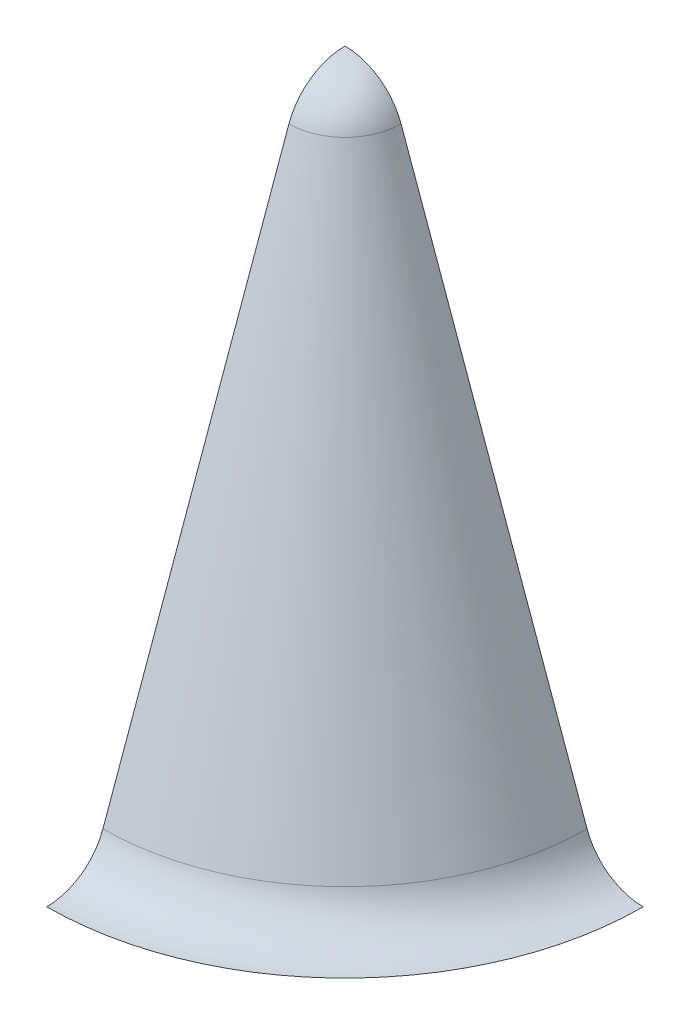
SolidWorks part; units mm, degrees
ref_plane "Ebene vorne" through (0, 0, 0) normal (0, 0, 1) x (1, 0, 0)
ref_plane "Ebene oben" through (0, 0, 0) normal (0, 1, 0) x (1, 0, 0)
ref_plane "Ebene rechts" through (0, 0, 0) normal (1, 0, 0) x (0, 0, -1)
sketch "Skizze2" plane through (0, 0, 0) normal (1, 0, 0) x (0, 0, -1)
  line L0 (0, 0) -> (1000, 0)
  line L1 (1000, 0) -> (1000, 2000)
  line L2 (1000, 2000) -> (1823.9706, 2000) construction
  line L3 (0, 0) -> (-711.6365, 0) construction
  line L4 (188.2165, 132.3647) -> (811.7835, 1867.6353)
  arc A0 (1000, 2000) -> (811.7835, 1867.6353) centre (1000, 1800) ccw
  arc A1 (0, 0) -> (188.2165, 132.3647) centre (0, 200) ccw
  point P10 (468.2367, 420.6035)
  dimension "D3" = 200
  dimension "D4" = 200
  dimension "D1" = 2000
  dimension "D2" = 1000
revolve "Rotation1" add sketch "Skizze2" angle 360 about L1
sketch "Skizze3" plane through (0, 0, 0) normal (0, 1, 0) x (1, 0, 0)
  line L0 (0, 0) -> (0, 1000)
  line L1 (0, 1000) -> (1000, 1000)
  arc A0 (0, 0) -> (1000, 1000) centre (0, 1000) cw
  dimension "D1" = 1000
  dimension "D3" = 1000
  dimension "D2" = 1000
extrude "Schnitt-Linear austragen1" cut sketch "Skizze3" along normal blind 4000
